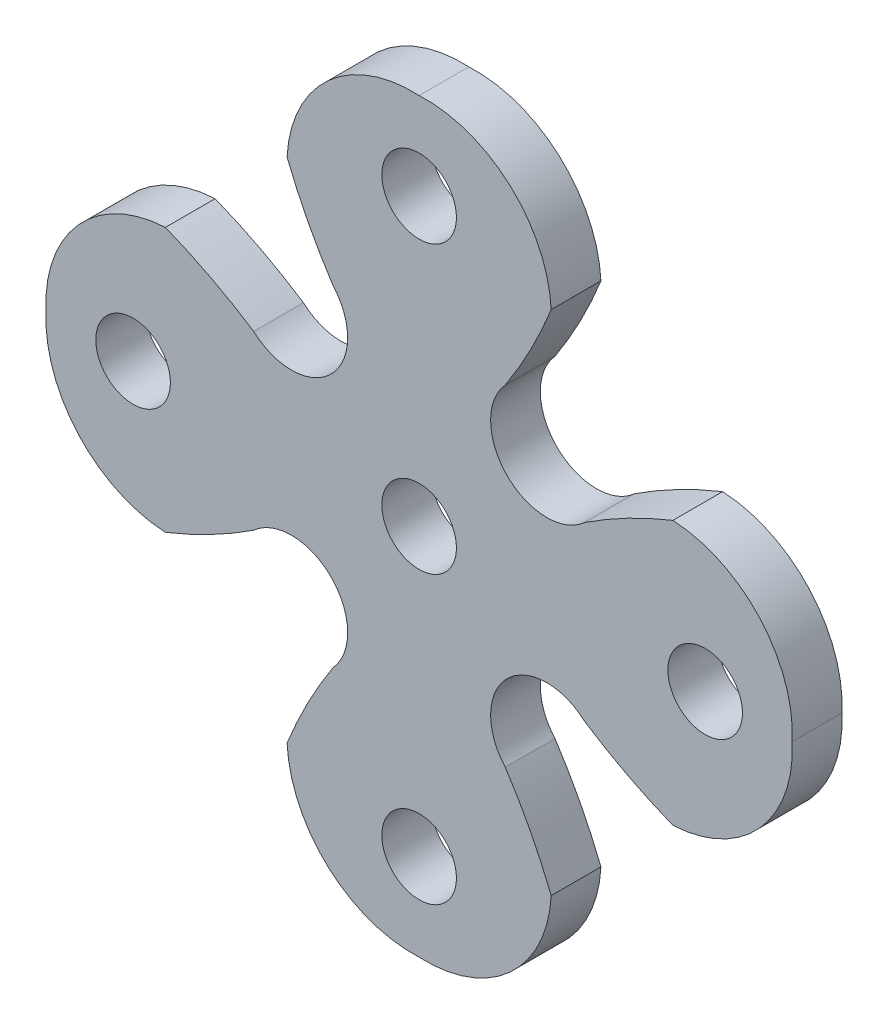
SolidWorks part; units mm, degrees
ref_plane "Front Plane" through (0, 0, 0) normal (0, 0, 1) x (1, 0, 0)
ref_plane "Top Plane" through (0, 0, 0) normal (0, 1, 0) x (1, 0, 0)
ref_plane "Right Plane" through (0, 0, 0) normal (1, 0, 0) x (0, 0, -1)
sketch "Sketch1" plane through (0, 0, 0) normal (0, 0, 1) x (1, 0, 0)
  line L0 (0, 0) -> (0, 19.05) construction
  line L1 (0, 0) -> (-35355.3391, -35355.3391) construction
  line L2 (0, 0) -> (-35355.3391, 35355.3391) construction
  circle A0 centre (0, 0) radius 19.05 construction
  circle A1 centre (0, 14.605) radius 1.905
  circle A2 centre (14.605, 0) radius 1.905
  circle A3 centre (0, -14.605) radius 1.905
  circle A4 centre (-14.605, 0) radius 1.905
  circle A5 centre (0, 0) radius 1.905
  circle A6 centre (0, 0) radius 6.35 construction
  circle A7 centre (0, 14.605) radius 4.445 construction
  circle A8 centre (0, 0) radius 14.605 construction
  circle A9 centre (10.3273, 10.3273) radius 4.445 construction
  circle A10 centre (10.3273, -10.3273) radius 4.445 construction
  circle A11 centre (-10.3273, -10.3273) radius 4.445 construction
  circle A12 centre (-10.3273, 10.3273) radius 4.445 construction
  arc A13 (-6.7425, 12.9555) -> (0, 19.05) centre (-0.324, 12.6315) cw
  arc A14 (6.7425, 12.9555) -> (0, 19.05) centre (0.324, 12.6315) ccw
  arc A15 (12.9555, 6.7425) -> (19.05, 0) centre (12.6315, 0.324) cw
  arc A16 (12.9555, -6.7425) -> (19.05, 0) centre (12.6315, -0.324) ccw
  arc A17 (6.7425, -12.9555) -> (0, -19.05) centre (0.324, -12.6315) cw
  arc A18 (-6.7425, -12.9555) -> (0, -19.05) centre (-0.324, -12.6315) ccw
  arc A19 (-12.9555, -6.7425) -> (-19.05, 0) centre (-12.6315, -0.324) cw
  arc A20 (-12.9555, 6.7425) -> (-19.05, 0) centre (-12.6315, 0.324) ccw
  circle A21 centre (0, 0) radius 9.525 construction
  arc A22 (-6.7425, 12.9555) -> (-4.3973, 8.4492) centre (16.8484, 22.3697) ccw
  arc A23 (6.7425, 12.9555) -> (4.3973, 8.4492) centre (-16.8484, 22.3697) cw
  arc A24 (12.9555, -6.7425) -> (8.4492, -4.3973) centre (22.3697, 16.8484) cw
  arc A25 (12.9555, 6.7425) -> (8.4492, 4.3973) centre (22.3697, -16.8484) ccw
  arc A26 (-6.7425, -12.9555) -> (-4.3973, -8.4492) centre (16.8484, -22.3697) cw
  arc A27 (6.7425, -12.9555) -> (4.3973, -8.4492) centre (-16.8484, -22.3697) ccw
  arc A28 (-12.9555, 6.7425) -> (-8.4492, 4.3973) centre (-22.3697, -16.8484) cw
  arc A29 (-12.9555, -6.7425) -> (-8.4492, -4.3973) centre (-22.3697, 16.8484) ccw
  arc A30 (-8.4492, 4.3973) -> (-4.3973, 8.4492) centre (-6.5183, 6.5183) ccw
  arc A31 (4.3973, 8.4492) -> (8.4492, 4.3973) centre (6.5183, 6.5183) ccw
  arc A32 (8.4492, -4.3973) -> (4.3973, -8.4492) centre (6.5183, -6.5183) ccw
  arc A33 (-4.3973, -8.4492) -> (-8.4492, -4.3973) centre (-6.5183, -6.5183) ccw
  point P15 (0, 0)
  point P32 (0, 0)
  point P52 (0, 0)
  point P76 (0, 0)
  point P81 (0, 0)
  dimension "D1" = 4.445
  dimension "D2" = 38.1
  dimension "D3" = 4
  dimension "D4" = 12.7
  dimension "D5" = 4
  dimension "D6" = 4
  dimension "D7" = 4
  dimension "D8" = 4
extrude "Boss-Extrude1" add sketch "Sketch1" along normal blind 2.54
